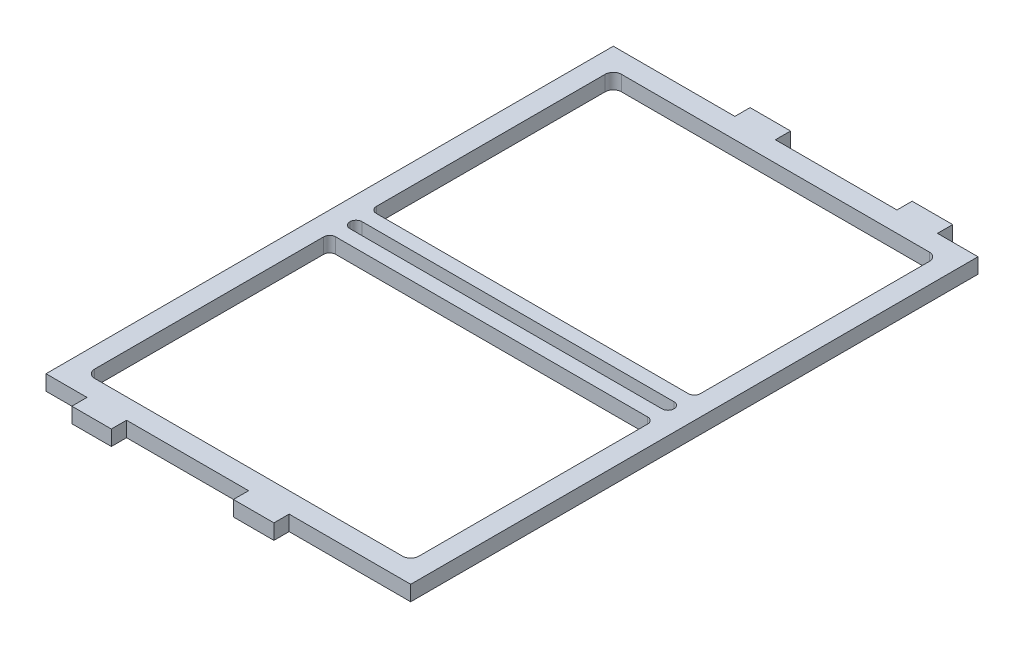
SolidWorks part; units mm, degrees
material "6061-T6 (SS)"
ref_plane "Front Plane" through (0, 0, 0) normal (0, 0, 1) x (1, 0, 0)
ref_plane "Top Plane" through (0, 0, 0) normal (0, 1, 0) x (1, 0, 0)
ref_plane "Right Plane" through (0, 0, 0) normal (1, 0, 0) x (0, 0, -1)
sketch "Sketch1" plane through (0, 0, 0) normal (0, 1, 0) x (1, 0, 0)
  line L0 (50.8, 82.55) -> (-50.8, 82.55)
  line L1 (57.15, 88.9) -> (-57.15, 88.9)
  line L2 (57.15, 88.9) -> (57.15, -88.9)
  line L3 (57.15, -88.9) -> (-57.15, -88.9)
  line L4 (-57.15, 88.9) -> (-57.15, -88.9)
  line L5 (57.15, 88.9) -> (-57.15, -88.9) construction
  line L6 (57.15, -88.9) -> (-57.15, 88.9) construction
  line L7 (-50.8, 82.55) -> (-50.8, -82.55)
  line L8 (50.8, -82.55) -> (-50.8, -82.55)
  line L9 (50.8, 82.55) -> (50.8, -82.55)
  point P0 (0, 0)
  dimension "D1" = 114.3
  dimension "D2" = 177.8
  dimension "D3" = 6.35
extrude "Boss-Extrude1" add sketch "Sketch1" along normal blind 4.7625
sketch "Sketch2" plane through (0, 0, 88.9) normal (0, 0, 1) x (1, 0, 0)
  line L0 (-57.15, 2.3813) -> (57.15, 2.3813) construction
  line L1 (-57.15, 4.7625) -> (-57.15, 0) construction
  line L2 (57.15, 4.7625) -> (57.15, 0) construction
  line L3 (-57.15, 0) -> (57.15, 0) construction
  line L4 (-31.9066, 4.7625) -> (-44.2934, 4.7625)
  line L5 (-31.9066, 4.7625) -> (-31.9066, 0)
  line L6 (-31.9066, 0) -> (-44.2934, 0)
  line L7 (-44.2934, 4.7625) -> (-44.2934, 0)
  line L8 (-31.9066, 4.7625) -> (-44.2934, 0) construction
  line L9 (-31.9066, 0) -> (-44.2934, 4.7625) construction
  line L11 (19.05, 4.7625) -> (6.35, 4.7625)
  line L12 (19.05, 4.7625) -> (19.05, 0)
  line L13 (19.05, 0) -> (6.35, 0)
  line L14 (6.35, 4.7625) -> (6.35, 0)
  line L15 (19.05, 4.7625) -> (6.35, 0) construction
  line L16 (19.05, 0) -> (6.35, 4.7625) construction
  point P6 (-38.1, 2.3813)
  point P13 (12.7, 2.3813)
  dimension "D1" = 19.05
  dimension "D2" = 50.8
  dimension "D3" = 12.7
extrude "Boss-Extrude2" add sketch "Sketch2" along normal blind 4.7625
sketch "Sketch3" plane through (0, 0, -88.9) normal (0, 0, -1) x (-1, 0, 0)
  line L0 (-57.15, 2.3813) -> (57.15, 2.3813) construction
  line L1 (-57.15, 4.7625) -> (-57.15, 0) construction
  line L2 (57.15, 4.7625) -> (57.15, 0) construction
  line L3 (-57.15, 0) -> (57.15, 0) construction
  line L4 (-31.75, 4.7625) -> (-44.45, 4.7625)
  line L5 (-31.75, 4.7625) -> (-31.75, 0)
  line L6 (-31.75, 0) -> (-44.45, 0)
  line L7 (-44.45, 4.7625) -> (-44.45, 0)
  line L8 (-31.75, 4.7625) -> (-44.45, 0) construction
  line L9 (-31.75, 0) -> (-44.45, 4.7625) construction
  line L11 (19.05, 4.7625) -> (6.35, 4.7625)
  line L12 (19.05, 4.7625) -> (19.05, 0)
  line L13 (19.05, 0) -> (6.35, 0)
  line L14 (6.35, 4.7625) -> (6.35, 0)
  line L15 (19.05, 4.7625) -> (6.35, 0) construction
  line L16 (19.05, 0) -> (6.35, 4.7625) construction
  point P6 (-38.1, 2.3812)
  point P13 (12.7, 2.3812)
  dimension "D1" = 12.7
  dimension "D2" = 12.7
  dimension "D3" = 19.05
  dimension "D4" = 50.8
extrude "Boss-Extrude3" add sketch "Sketch3" along normal blind 4.7625
fillet "Fillet1" radius 2.54 4 edges at (50.8, 2.3813, 82.55) (50.8, 2.3813, -82.55) (-50.8, 2.3813, -82.55) (-50.8, 2.3813, 82.55)
sketch "Sketch4" plane through (0, 0, 0) normal (0, -1, 0) x (1, 0, 0)
  line L0 (-48.26, 82.55) -> (48.26, 82.55) construction
  line L1 (-6.35, -82.55) -> (6.35, -82.55)
  line L2 (-6.35, -82.55) -> (-6.35, 82.55)
  line L3 (-6.35, 82.55) -> (6.35, 82.55)
  line L4 (6.35, -82.55) -> (6.35, 82.55)
  line L5 (-6.35, -82.55) -> (6.35, 82.55) construction
  line L6 (-6.35, 82.55) -> (6.35, -82.55) construction
  line L7 (1.905, 76.2) -> (-1.905, 76.2) construction
  line L8 (1.905, -76.2) -> (-1.905, -76.2) construction
  line L9 (-1.905, -76.2) -> (-1.905, 76.2)
  line L11 (1.905, -76.2) -> (1.905, 76.2)
  line L12 (-1.905, -76.2) -> (1.905, 76.2) construction
  line L13 (-1.905, 76.2) -> (1.905, -76.2) construction
  arc A0 (1.905, -76.2) -> (-1.905, -76.2) centre (0, -76.2) cw
  arc A1 (1.905, 76.2) -> (-1.905, 76.2) centre (0, 76.2) ccw
  point P0 (0, 0)
  point P8 (0, 0)
  dimension "D4" = 1.905
  dimension "D1" = 12.7
  dimension "D2" = 3.81
  dimension "D3" = 152.4
extrude "Boss-Extrude4" [suppressed] add sketch "Sketch4" against normal blind 4.7625
fillet "Fillet2" [suppressed] radius 2.54
sketch "Sketch5" plane through (0, 0, 0) normal (0, -1, 0) x (1, 0, 0)
  line L0 (57.15, 88.9) -> (57.15, -88.9) construction
  line L1 (-57.15, -6.35) -> (57.15, -6.35)
  line L2 (-57.15, -6.35) -> (-57.15, 6.35)
  line L3 (-57.15, 6.35) -> (57.15, 6.35)
  line L4 (57.15, -6.35) -> (57.15, 6.35)
  line L5 (-57.15, -6.35) -> (57.15, 6.35) construction
  line L6 (-57.15, 6.35) -> (57.15, -6.35) construction
  line L8 (-50.8, -1.905) -> (50.8, -1.905)
  line L9 (-50.8, -1.905) -> (-50.8, 1.905)
  line L10 (-50.8, 1.905) -> (50.8, 1.905)
  line L11 (50.8, -1.905) -> (50.8, 1.905)
  line L12 (-50.8, -1.905) -> (50.8, 1.905) construction
  line L13 (-50.8, 1.905) -> (50.8, -1.905) construction
  point P0 (0, 0)
  point P8 (0, 0)
  dimension "D1" = 12.7
  dimension "D2" = 101.6
  dimension "D3" = 3.81
extrude "Boss-Extrude5" add sketch "Sketch5" against normal blind 4.7625
fillet "Fillet3" radius 1.905 8 edges at (50.8, 2.3813, 6.35) (-50.8, 2.3813, 6.35) (-50.8, 2.3813, -6.35) (50.8, 2.3813, -6.35) (50.8, 2.3813, -1.905) (50.8, 2.3813, 1.905) (-50.8, 2.3813, -1.905) (-50.8, 2.3813, 1.905)
